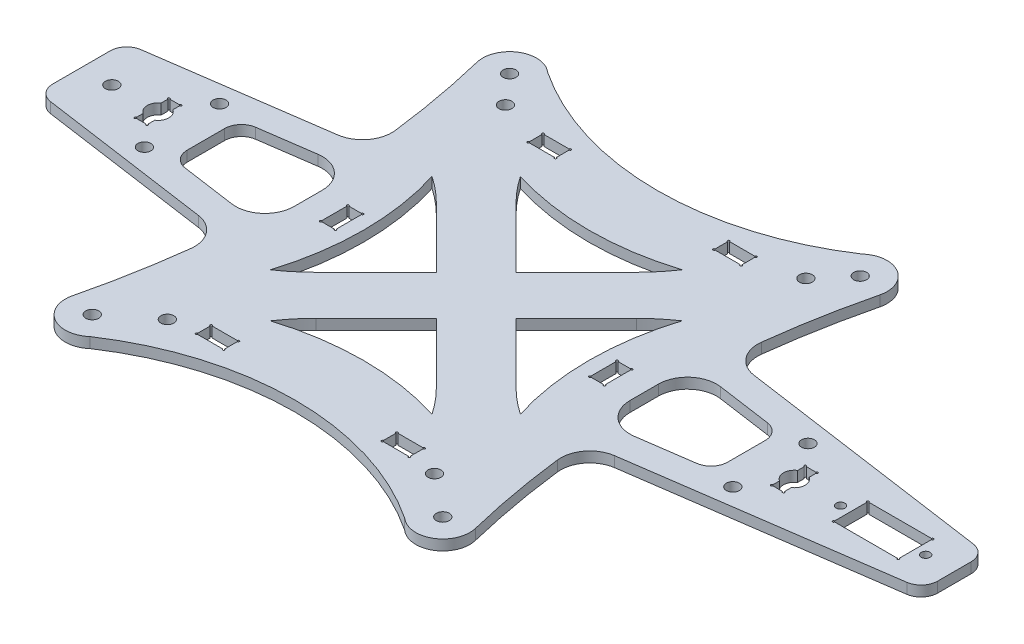
SolidWorks part; units mm, degrees
material "PPS"
ref_plane "前视基准面" through (0, 0, 0) normal (0, 0, 1) x (1, 0, 0)
ref_plane "上视基准面" through (0, 0, 0) normal (0, 1, 0) x (1, 0, 0)
ref_plane "右视基准面" through (0, 0, 0) normal (1, 0, 0) x (0, 0, -1)
sketch "草图1" plane through (0, 0, 0) normal (0, 1, 0) x (1, 0, 0)
  line L3 (-133.7177, 0) -> (146.3754, 0) construction
  line L56 (0, 96.0639) -> (0, -115.1457) construction
  line L65 (-25.5, 41.5) -> (-19, 41.5)
  line L66 (-34, 3.25) -> (-30.5, 3.25)
  line L70 (-34, 3.25) -> (-34, -3.25)
  line L76 (-34, -3.25) -> (-30.5, -3.25)
  line L80 (-30.5, 3.25) -> (-30.5, -3.25)
  line L81 (-25.5, -38) -> (-19, -38)
  line L82 (-25.5, -38) -> (-25.5, -41.5)
  line L83 (-25.5, -41.5) -> (-19, -41.5)
  line L84 (-19, -38) -> (-19, -41.5)
  line L85 (-19, 38) -> (-19, 41.5)
  line L86 (-25.5, 38) -> (-19, 38)
  line L142 (-25.5, 38) -> (-25.5, 41.5)
  line L143 (25.5, 38) -> (25.5, 41.5)
  line L144 (25.5, 38) -> (19, 38)
  line L145 (19, 38) -> (19, 41.5)
  line L146 (19, -38) -> (19, -41.5)
  line L147 (25.5, -41.5) -> (19, -41.5)
  line L148 (25.5, -38) -> (25.5, -41.5)
  line L149 (25.5, -38) -> (19, -38)
  line L150 (30.5, 3.25) -> (30.5, -3.25)
  line L151 (34, -3.25) -> (30.5, -3.25)
  line L152 (34, 3.25) -> (34, -3.25)
  line L153 (34, 3.25) -> (30.5, 3.25)
  line L154 (25.5, 41.5) -> (19, 41.5)
  line L155 (77.65, -2.1518) -> (77.65, -4)
  line L156 (74.85, 4) -> (77.65, 4)
  line L157 (74.85, 4) -> (74.85, 2.1768)
  line L158 (74.85, -4) -> (77.65, -4)
  line L159 (77.65, 4) -> (77.65, 2.1518)
  line L160 (74.85, -2.1768) -> (74.85, -4)
  line L161 (97.5, 7.6653) -> (97.5, -9.1503) construction
  line L162 (89.75, 4.1) -> (105.25, 4.1)
  line L163 (89.75, 4.1) -> (89.75, -4.1)
  line L164 (89.75, -4.1) -> (105.25, -4.1)
  line L165 (105.25, 4.1) -> (105.25, -4.1)
  line L166 (-97.5, 7.6653) -> (-97.5, -9.1503) construction
  line L171 (-74.85, -2.1768) -> (-74.85, -4)
  line L172 (-77.65, 4) -> (-77.65, 2.1518)
  line L173 (-74.85, -4) -> (-77.65, -4)
  line L174 (-74.85, 4) -> (-74.85, 2.1768)
  line L175 (-74.85, 4) -> (-77.65, 4)
  line L176 (-77.65, -2.1518) -> (-77.65, -4)
  line L177 (114.5911, 7.4683) -> (114.5911, -7.4683)
  line L178 (114.5911, 7.4683) -> (43.1936, 17.6463)
  line L179 (114.5911, -7.4683) -> (43.1936, -17.6463)
  line L183 (-23.978, 14.4296) -> (-9.5485, 0)
  line L184 (14.4296, 23.978) -> (0, 9.5485)
  line L185 (-23.978, -14.4296) -> (-9.5485, 0)
  line L186 (-14.4296, 23.978) -> (0, 9.5485)
  line L187 (23.978, -14.4296) -> (9.5485, 0)
  line L188 (23.978, 14.4296) -> (9.5485, 0)
  line L189 (-14.4296, -23.978) -> (0, -9.5485)
  line L190 (14.4296, -23.978) -> (0, -9.5485)
  line L191 (-94.5795, 10.321) -> (-94.5795, -10.321)
  line L192 (-43.1936, 17.6463) -> (-94.5795, 10.321)
  line L193 (-94.5795, -10.321) -> (-43.1936, -17.6463)
  line L195 (-64.75, -7.9571) -> (-64.75, 7.9571)
  line L196 (-64.75, 7.9571) -> (-40.25, 11.4497)
  line L197 (-40.25, 11.4497) -> (-40.25, -11.4497)
  line L198 (-64.75, -7.9571) -> (-40.25, -11.4497)
  line L199 (64.75, 7.9571) -> (40.25, 11.4497)
  line L200 (40.25, 11.4497) -> (40.25, -11.4497)
  line L201 (64.75, -7.9571) -> (40.25, -11.4497)
  line L202 (64.75, 7.9571) -> (64.75, -7.9571)
  circle A0 centre (-36, 43) radius 1.55
  circle A1 centre (-32, -42) radius 1.55
  circle A2 centre (32, -42) radius 1.55
  circle A3 centre (36, 43) radius 1.55
  circle A4 centre (42, 50) radius 1.55
  circle A5 centre (42, -50) radius 1.55
  circle A6 centre (-42, -50) radius 1.55
  circle A7 centre (-42, 50) radius 1.55
  arc A8 (74.85, 2.1768) -> (74.85, -2.1768) centre (76.2307, 0) ccw
  arc A9 (77.65, -2.1518) -> (77.65, 2.1518) centre (76.2307, 0) ccw
  circle A10 centre (107.7, 0) radius 1.05
  circle A11 centre (87.3, 0) radius 1.05
  circle A12 centre (-87.3, 0) radius 1.05 construction
  arc A14 (-77.65, -2.1518) -> (-77.65, 2.1518) centre (-76.2307, 0) cw
  arc A15 (-74.85, 2.1768) -> (-74.85, -2.1768) centre (-76.2307, 0) cw
  arc A18 (-37.7098, 54.831) -> (37.7098, 54.831) centre (0, 111.5317) ccw
  arc A20 (48.2756, 48.4632) -> (43.1936, 17.6463) centre (246.1791, 0) ccw
  arc A21 (48.2756, 48.4632) -> (37.7098, 54.831) centre (42, 50) ccw
  arc A22 (-37.7098, -54.831) -> (37.7098, -54.831) centre (0, -111.5317) cw
  arc A23 (48.2756, -48.4632) -> (43.1936, -17.6463) centre (246.1791, 0) cw
  arc A24 (48.2756, -48.4632) -> (37.7098, -54.831) centre (42, -50) cw
  arc A26 (-48.2756, -48.4632) -> (-37.7098, -54.831) centre (-42, -50) ccw
  arc A27 (-48.2756, -48.4632) -> (-43.1936, -17.6463) centre (-246.1791, 0) ccw
  arc A28 (-48.2756, 48.4632) -> (-37.7098, 54.831) centre (-42, 50) cw
  arc A30 (-48.2756, 48.4632) -> (-43.1936, 17.6463) centre (-246.1791, 0) cw
  arc A31 (-23.978, 14.4296) -> (-29.9602, 19.3706) centre (-52.8883, -14.4807) ccw
  arc A32 (-23.978, -14.4296) -> (-29.9602, -19.3706) centre (-52.8883, 14.4807) cw
  arc A33 (-29.9602, -19.3706) -> (-29.9602, 19.3706) centre (-91.9966, 0) ccw
  arc A34 (-14.4296, 23.978) -> (-19.3706, 29.9602) centre (14.4807, 52.8883) cw
  arc A35 (-19.3706, 29.9602) -> (19.3706, 29.9602) centre (0, 91.9966) ccw
  arc A36 (14.4296, 23.978) -> (19.3706, 29.9602) centre (-14.4807, 52.8883) ccw
  arc A37 (23.978, 14.4296) -> (29.9602, 19.3706) centre (52.8883, -14.4807) cw
  arc A38 (29.9602, 19.3706) -> (29.9602, -19.3706) centre (91.9966, 0) ccw
  arc A39 (23.978, -14.4296) -> (29.9602, -19.3706) centre (52.8883, 14.4807) ccw
  arc A40 (14.4296, -23.978) -> (19.3706, -29.9602) centre (-14.4807, -52.8883) cw
  arc A41 (19.3706, -29.9602) -> (-19.3706, -29.9602) centre (0, -91.9966) ccw
  arc A42 (-14.4296, -23.978) -> (-19.3706, -29.9602) centre (14.4807, -52.8883) ccw
  circle A43 centre (70.5, 9) radius 1.55
  circle A44 centre (70.5, -9) radius 1.55
  circle A45 centre (-70.5, -9) radius 1.55
  circle A46 centre (-70.5, 9) radius 1.55
  circle A47 centre (-87.3, 0) radius 1.55
  point P81 (-34, 0)
  point P118 (0, 0)
  point P140 (-40.25, 0)
  point P149 (-64.75, 0)
  dimension "D5" = 38
  dimension "D18" = 8.2
  dimension "D24" = 3.1
  dimension "D6" = 3.1
  dimension "D11" = 50
  dimension "D15" = 74.85
  dimension "D16" = 2.1
  dimension "D17" = 15.5
  dimension "D21" = 3.1
  dimension "D1" = 6.5
  dimension "D2" = 3.5
  dimension "D3" = 30.5
  dimension "D4" = 19
  dimension "D7" = 32
  dimension "D8" = 42
  dimension "D9" = 43
  dimension "D10" = 36
  dimension "D12" = 42
  dimension "D13" = 2.8
  dimension "D14" = 4
  dimension "D19" = 2.45
  dimension "D20" = 97.5
  dimension "D22" = 9
  dimension "D23" = 70.5
  dimension "D25" = 6.55
  dimension "D26" = 5.75
  dimension "D27" = 6.25
  dimension "D28" = 4
extrude "凸台-拉伸1" add sketch "草图1" along normal blind 2.5
fillet "圆角1" radius 4 8 edges at (114.5911, 1.25, -7.4683) (114.5911, 1.25, 7.4683) (-94.5795, 1.25, 10.321) (-94.5795, 1.25, -10.321) (-64.75, 1.25, 7.9571) (-64.75, 1.25, -7.9571) (64.75, 1.25, 7.9571) (64.75, 1.25, -7.9571)
fillet "圆角2" radius 7 8 edges at (43.1936, 1.25, -17.6463) (43.1936, 1.25, 17.6463) (-43.1936, 1.25, 17.6463) (-43.1936, 1.25, -17.6463) (40.25, 1.25, 11.4497) (40.25, 1.25, -11.4497) (-40.25, 1.25, 11.4497) (-40.25, 1.25, -11.4497)
sketch "草图2" plane through (0, 2.5, 0) normal (0, 1, 0) x (1, 0, 0)
  line L0 (0, 0) -> (0, -66.7571) construction
  circle A0 centre (-77.65, 4) radius 0.25
  circle A1 centre (-74.85, 4) radius 0.25
  circle A2 centre (-77.65, -4) radius 0.25
  circle A3 centre (-74.85, -4) radius 0.25
  circle A4 centre (-25.5, 41.5) radius 0.25
  circle A5 centre (-19, 41.5) radius 0.25
  circle A6 centre (-25.5, 38) radius 0.25
  circle A7 centre (-19, 38) radius 0.25
  circle A8 centre (-34, 3.25) radius 0.25
  circle A9 centre (-30.5, 3.25) radius 0.25
  circle A10 centre (-34, -3.25) radius 0.25
  circle A11 centre (-30.5, -3.25) radius 0.25
  circle A12 centre (-25.5, -38) radius 0.25
  circle A13 centre (-19, -38) radius 0.25
  circle A14 centre (-25.5, -41.5) radius 0.25
  circle A15 centre (-19, -41.5) radius 0.25
  circle A16 centre (19, -41.5) radius 0.25
  circle A17 centre (25.5, -41.5) radius 0.25
  circle A18 centre (19, -38) radius 0.25
  circle A19 centre (25.5, -38) radius 0.25
  circle A20 centre (30.5, -3.25) radius 0.25
  circle A21 centre (34, -3.25) radius 0.25
  circle A22 centre (30.5, 3.25) radius 0.25
  circle A23 centre (34, 3.25) radius 0.25
  circle A24 centre (19, 38) radius 0.25
  circle A25 centre (25.5, 38) radius 0.25
  circle A26 centre (19, 41.5) radius 0.25
  circle A27 centre (25.5, 41.5) radius 0.25
  circle A28 centre (74.85, -4) radius 0.25
  circle A29 centre (77.65, -4) radius 0.25
  circle A30 centre (74.85, 4) radius 0.25
  circle A31 centre (77.65, 4) radius 0.25
  circle A32 centre (89.75, 4.1) radius 0.25
  circle A33 centre (105.25, 4.1) radius 0.25
  circle A34 centre (89.75, -4.1) radius 0.25
  circle A35 centre (105.25, -4.1) radius 0.25
  dimension "D1" = 0.5
extrude "切除-拉伸1" cut sketch "草图2" against normal through all
